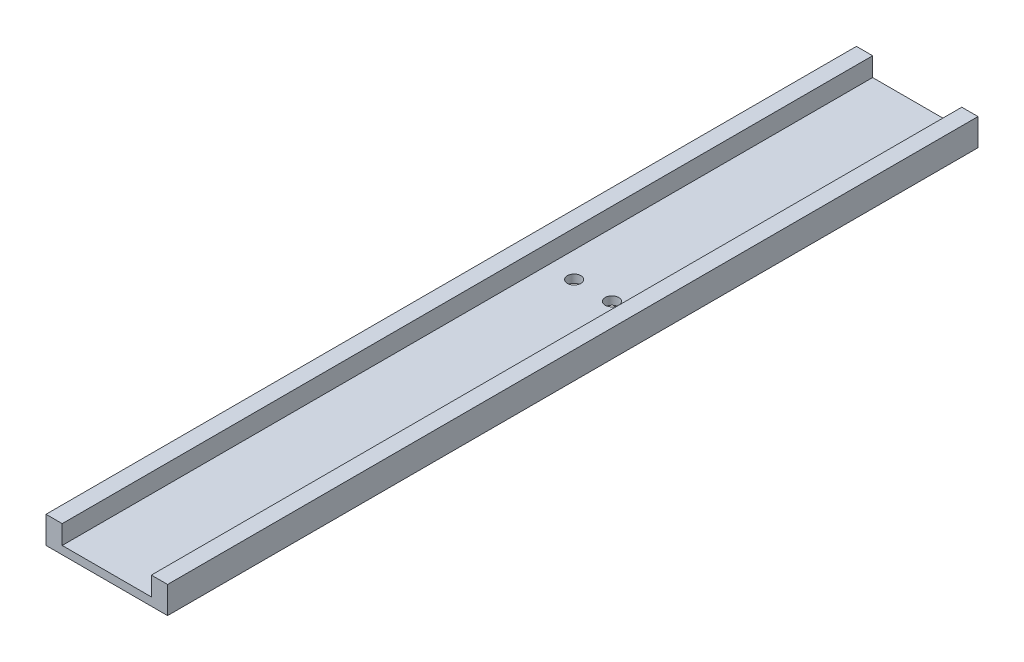
SolidWorks part; units mm, degrees
other "Objet de détail1"
ref_plane "Front" through (0, 0, 0) normal (0, 0, 1) x (1, 0, 0)
ref_plane "Top" through (0, 0, 0) normal (0, 1, 0) x (1, 0, 0)
ref_plane "Right" through (0, 0, 0) normal (1, 0, 0) x (0, 0, -1)
sketch "Esquisse1" plane through (0, 0, 0) normal (0, 0, 1) x (1, 0, 0)
  line L0 (0, 0) -> (0, 10)
  line L1 (0, 10) -> (6, 10)
  line L2 (45, 10) -> (39, 10)
  line L4 (6, 10) -> (6, 3)
  line L5 (6, 3) -> (39, 3)
  line L6 (0, 0) -> (45, 0)
  line L7 (22.5, 0) -> (22.5, 3) construction
  line L8 (39, 10) -> (39, 3)
  line L12 (45, 0) -> (45, 10)
  dimension "D1" = 33
  dimension "D2" = 3
  dimension "D3" = 6
  dimension "D4" = 10
extrude "Boss.-Extru.1" add sketch "Esquisse1" along normal blind 300
sketch "Esquisse2" plane through (0, 3, 0) normal (0, 1, 0) x (1, 0, 0)
  line L0 (22.5, -300) -> (22.5, -120) construction
  line L1 (39, -300) -> (6, -300) construction
  line L2 (22.5, -120) -> (15.5, -120) construction
  circle A0 centre (15.5, -120) radius 2.5
  circle A1 centre (29.5, -120) radius 2.5
  dimension "D1" = 5
  dimension "D2" = 14
  dimension "D3" = 180
extrude "Enlèv. mat.-Extru.1" cut sketch "Esquisse2" against normal through all both and the other way through all
